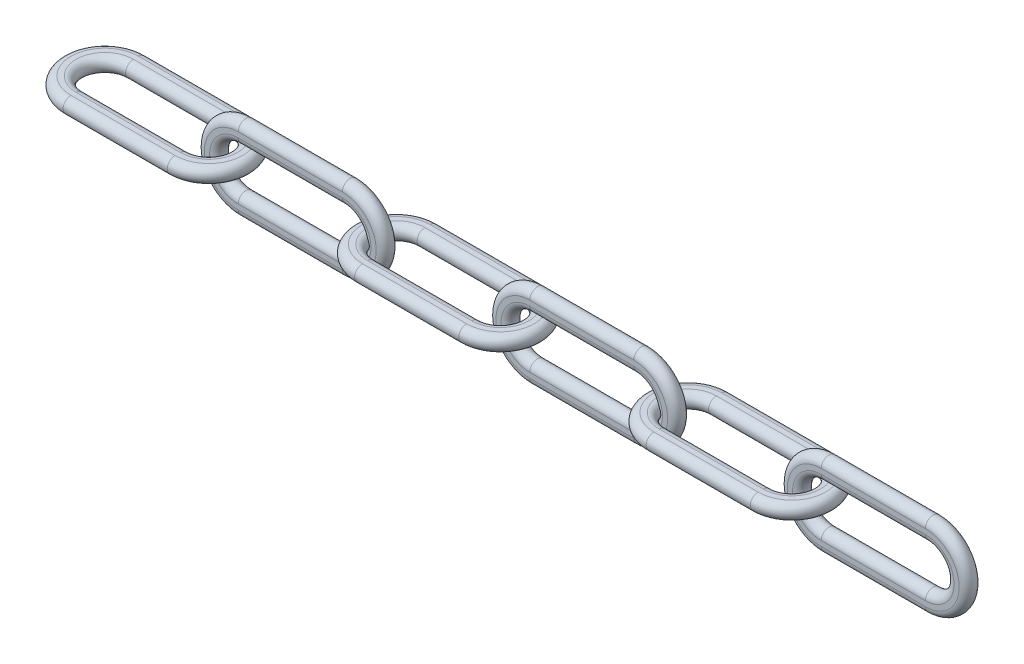
SolidWorks part; units mm, degrees
ref_plane "Piano frontale" through (0, 0, 0) normal (0, 0, 1) x (1, 0, 0)
ref_plane "Piano superiore" through (0, 0, 0) normal (0, 1, 0) x (1, 0, 0)
ref_plane "Piano destro" through (0, 0, 0) normal (1, 0, 0) x (0, 0, -1)
sketch "Schizzo1" plane through (0, 0, 0) normal (0, 1, 0) x (1, 0, 0)
  line L0 (-7.0609, 0) -> (2.9391, 0) construction
  line L1 (-7.0609, 4) -> (2.9391, 4)
  line L2 (-7.0609, -4) -> (2.9391, -4)
  line L3 (-7.0609, 2) -> (2.9391, 2)
  line L4 (-7.0609, -2) -> (2.9391, -2)
  arc A0 (-7.0609, 4) -> (-7.0609, -4) centre (-7.0609, 0) ccw
  arc A1 (2.9391, -4) -> (2.9391, 4) centre (2.9391, 0) ccw
  arc A2 (2.9391, -2) -> (2.9391, 2) centre (2.9391, 0) ccw
  arc A3 (-7.0609, 2) -> (-7.0609, -2) centre (-7.0609, 0) ccw
  point P3 (-2.0609, 0)
  dimension "D2" = 4
  dimension "D3" = 2
  dimension "D1" = 10
extrude "Estrusione-Estrusione1" add sketch "Schizzo1" along normal blind 1.5
fillet "Raccordo9" 2 edges at (-2.0609, 0, -4) (-2.0609, 1.5, -4) type full round first side face at (-2.0609, 0, 0) second side face at (-2.0609, 1.5, 0) middle face at (-2.0609, 0.75, -4)
fillet "Raccordo13" 2 edges at (-2.0609, 1.5, -2) (-2.0609, 0, -2) type full round first side face at (-2.0609, 1.5, 0) second side face at (-2.0609, 0, 0) middle face at (-2.0609, 0.75, -2)
sketch "Schizzo2" plane through (0, 0, 0) normal (0, 1, 0) x (1, 0, 0)
  line L0 (-2.5843, 8.9767) -> (-2.5843, -11.7532) construction
  line L1 (-16.4583, 0) -> (14.3127, 0) construction
sketch "Schizzo3" plane through (0, 0, 0) normal (0, 0, 1) x (1, 0, 0)
  line L0 (6.5071, 0.75) -> (16.5071, 0.75) construction
  line L1 (6.5071, 4.75) -> (16.5071, 4.75)
  line L2 (6.5071, 2.75) -> (16.5071, 2.75)
  line L3 (6.5071, -1.25) -> (16.5071, -1.25)
  line L4 (6.5071, -3.25) -> (16.5071, -3.25)
  arc A0 (6.5071, 2.75) -> (6.5071, -1.25) centre (6.5071, 0.75) ccw
  arc A1 (16.5071, -1.25) -> (16.5071, 2.75) centre (16.5071, 0.75) ccw
  arc A2 (16.5071, -3.25) -> (16.5071, 4.75) centre (16.5071, 0.75) ccw
  arc A3 (6.5071, 4.75) -> (6.5071, -3.25) centre (6.5071, 0.75) ccw
  point P2 (11.5071, 0.75)
  dimension "D2" = 2
  dimension "D1" = 10
extrude "Estrusione-Estrusione2" add sketch "Schizzo3" along normal mid plane 1.5
fillet "Raccordo16" 2 edges at (11.5071, 4.75, 0.75) (11.5071, 4.75, -0.75) type full round first side face at (11.5071, 0.75, 0.75) second side face at (11.5071, 0.75, -0.75) middle face at (11.5071, 4.75, 0)
fillet "Raccordo17" 2 edges at (11.5071, -1.25, -0.75) (11.5071, -1.25, 0.75) type full round first side face at (11.5071, 0.75, -0.75) second side face at (11.5071, 0.75, 0.75) middle face at (11.5071, -1.25, 0)
pattern_linear "Ripetizione a L2" count 3 spacing 28 along (1, 0, 0) of bodies 101
pattern_linear "Ripetizione a L3" count 3 spacing 28 along (1, 0, 0) of bodies 107
